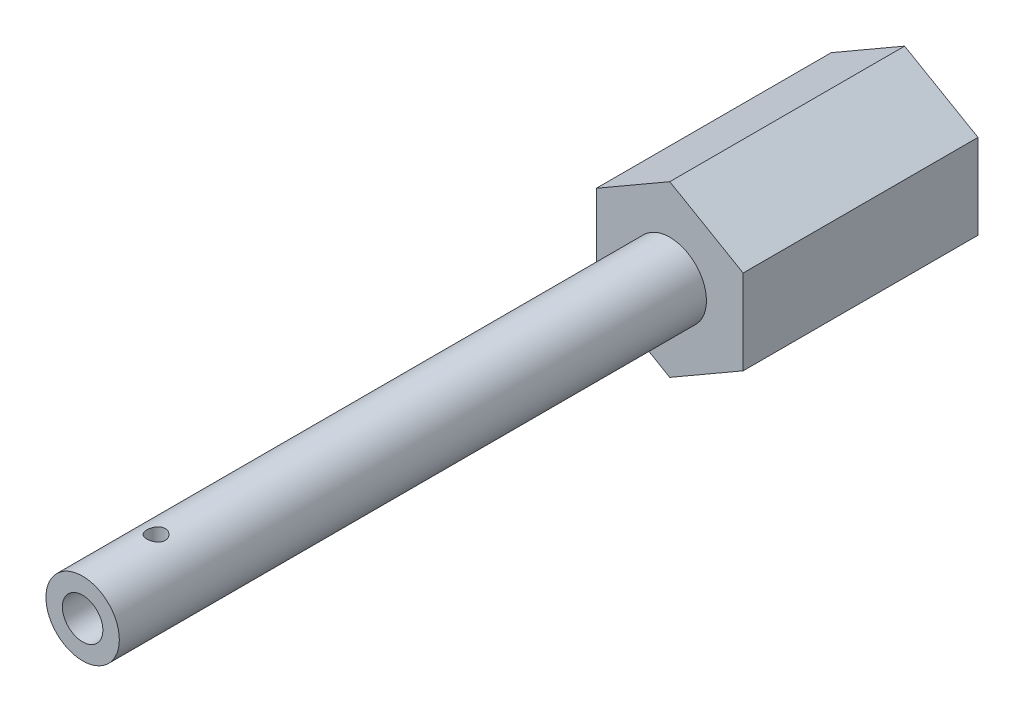
SolidWorks part; units mm, degrees
ref_plane "Front Plane" through (0, 0, 0) normal (0, 0, 1) x (1, 0, 0)
ref_plane "Top Plane" through (0, 0, 0) normal (0, 1, 0) x (1, 0, 0)
ref_plane "Right Plane" through (0, 0, 0) normal (1, 0, 0) x (0, 0, -1)
sketch "Sketch1" plane through (0, 0, 0) normal (0, 0, 1) x (1, 0, 0)
  line L1 (0, 7.3323) -> (-6.35, 3.6662)
  line L2 (-6.35, 3.6662) -> (-6.35, -3.6662)
  line L3 (-6.35, -3.6662) -> (0, -7.3323)
  line L4 (0, -7.3323) -> (6.35, -3.6662)
  line L5 (6.35, -3.6662) -> (6.35, 3.6662)
  line L6 (6.35, 3.6662) -> (0, 7.3323)
  circle A0 centre (0, 0) radius 6.35 construction
  dimension "D1" = 12.7
extrude "Boss-Extrude1" add sketch "Sketch1" along normal blind 20.32 contours L6 L1 L2 L3 L4 L5
sketch "Sketch2" plane through (0, 0, 20.32) normal (0, 0, 1) x (1, 0, 0)
  circle A0 centre (0, 0) radius 3.175
  dimension "D1" = 6.35
extrude "Boss-Extrude2" add sketch "Sketch2" along normal blind 50.8
hole_wizard "Ø3.5 (3.5) Diameter Hole1" positions "Sketch3" profile "Sketch4" hole size "Ø3.5" standard "ANSI Metric"
sketch "Sketch3" plane through (0, 0, 71.12) normal (0, 0, 1) x (1, 0, 0)
  point P0 (0, 0)
sketch "Sketch4" plane through (0, 0, 71.12) normal (1, 0, 0) x (0, -1, 0)
  line L0 (0, 0) -> (0, 26.4515)
  line L1 (0, 26.4515) -> (1.75, 25.4)
  line L2 (1.75, 25.4) -> (1.75, 0)
  line L5 (1.75, 0) -> (0, 0)
  line L10 (0, 26.4515) -> (-1.75, 25.4) construction
  line L11 (0, -6.35) -> (0, 107.95) construction
  dimension "Hole Dia." = 3.5
  dimension "Hole Depth" = 25.4
  dimension "Drill Angle" = 118
ref_plane "Plane1" through (0, 7.62, 0) normal (0, 1, 0) x (1, 0, 0)
hole_wizard "1/16 (0.0625) Diameter Hole1" positions "Sketch5" profile "Sketch6" hole size "1/16" standard "ANSI Inch" end condition through all
sketch "Sketch5" plane through (0, 7.62, 0) normal (0, 1, 0) x (1, 0, 0)
  line L0 (-3.175, -71.12) -> (3.175, -71.12) construction
  point P0 (0, -64.77)
  dimension "D1" = 6.35
sketch "Sketch6" plane through (0, 7.62, 64.77) normal (1, 0, 0) x (0, 0, 1)
  line L0 (0, 0) -> (0, 14.9523)
  line L1 (0, 14.9523) -> (0.7937, 14.9523)
  line L2 (0.7937, 14.9523) -> (0.7937, 0)
  line L5 (0.7937, 0) -> (0, 0)
  line L11 (0, -6.35) -> (0, 107.95) construction
  dimension "Thru Hole Dia." = 1.5875
  dimension "Thru Hole Depth" = 14.9523
